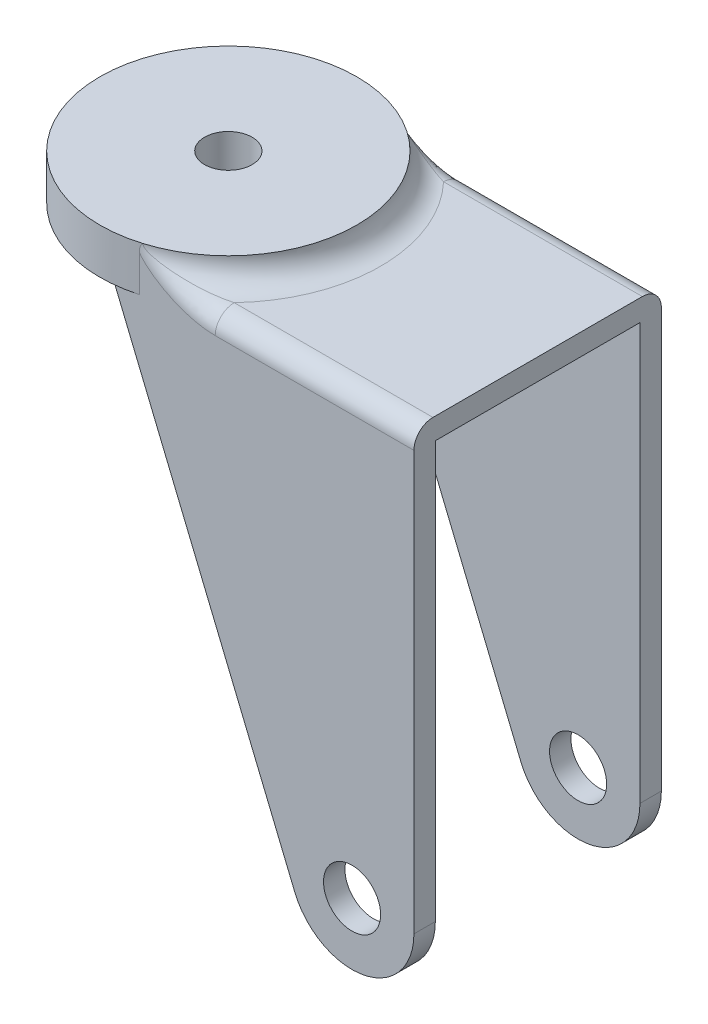
SolidWorks part; units mm, degrees
ref_plane "Plano frontal" through (0, 0, 0) normal (0, 0, 1) x (1, 0, 0)
ref_plane "Plano superior" through (0, 0, 0) normal (0, 1, 0) x (1, 0, 0)
ref_plane "Plano direito" through (0, 0, 0) normal (1, 0, 0) x (0, 0, -1)
sketch "Esboço10" plane through (0, 0, 0) normal (0, 0, 1) x (1, 0, 0)
  line L0 (0, 0) -> (0, 92) construction
  line L1 (-13, 0) -> (13, 0) construction
  line L2 (0, 92) -> (13, 92) construction
  line L4 (0, 68) -> (13, 68) construction
  line L7 (13, 92) -> (-52, 92)
  line L8 (-52, 92) -> (-12.0183, -4.956)
  line L9 (13, 0) -> (13, 92)
  line L11 (4.2426, 4.2426) -> (0, 0) construction
  line L15 (13, 92) -> (0.2553, 92)
  circle A0 centre (0, 0) radius 6
  circle A1 centre (0, 0) radius 13 construction
  arc A5 (-12.0183, -4.956) -> (13, 0) centre (0, 0) ccw
  dimension "D3" = 12
  dimension "D4" = 7
  dimension "D1" = 92
  dimension "D2" = 65
  dimension "D5" = 68
extrude "Ressalto-extrusão1" add sketch "Esboço10" along normal blind 26 and the other way blind 26 contours L15 L8 A5 A0 region at (-10.9262, 50.1469, 0)
shell "Casca2" thickness 4.5 removed face at (-32.0091, 43.522, 0) removed face at (1.5085, -7.6151, 0) removed face at (13, 46, 0)
sketch "Esboço11" plane through (13, 0, 0) normal (1, 0, 0) x (0, 0, -1)
  line L0 (21.5, 0) -> (21.5, 87.5) construction
  line L1 (-21.5, 87.5) -> (21.5, 87.5)
  line L2 (-21.5, 87.5) -> (-21.5, -37.1848)
  line L3 (-21.5, -37.1848) -> (21.5, -37.1848)
  line L4 (21.5, 87.5) -> (21.5, -37.1848)
extrude "Corte-extrusão1" cut sketch "Esboço11" against normal through all both and the other way through all
sketch "Esboço12" plane through (0, 92, 0) normal (0, 1, 0) x (1, 0, 0)
  line L0 (-52, 26) -> (-52, -26) construction
  circle A0 centre (-52, 0) radius 27
  dimension "D1" = 54
extrude "Ressalto-extrusão2" add sketch "Esboço12" along normal blind 5 and the other way blind 4.5
sketch "Esboço13" plane through (0, 97, 0) normal (0, 1, 0) x (1, 0, 0)
  circle A0 centre (-52, 0) radius 5
  dimension "D1" = 10
extrude "Corte-extrusão2" cut sketch "Esboço13" against normal through all both and the other way through all
fillet "Filete6" radius 5 1 edges at (-25, 92, 0)
fillet "Filete7" radius 4 4 edges at (-44.2119, 95.8194, -26) (-43.5704, 95.2075, 26) (-10.1726, 92, -26) (-10.1726, 92, 26)
